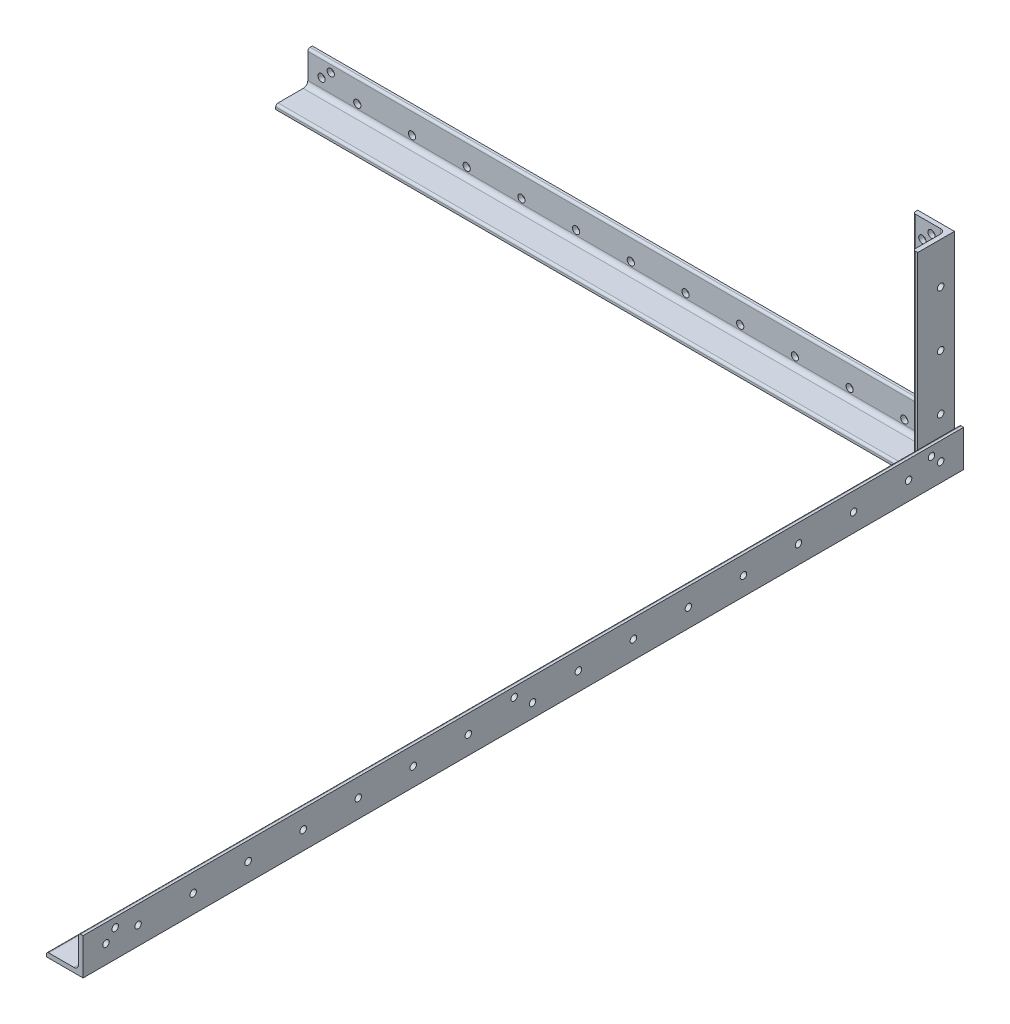
SolidWorks part; units mm, degrees
ref_plane "Front Plane" through (0, 0, 0) normal (0, 0, 1) x (1, 0, 0)
ref_plane "Top Plane" through (0, 0, 0) normal (0, 1, 0) x (1, 0, 0)
ref_plane "Right Plane" through (0, 0, 0) normal (1, 0, 0) x (0, 0, -1)
sketch "Sketch0" plane through (0, 0, 0) normal (0, 0, 1) x (1, 0, 0)
  line L0 (-12.7, -12.7) -> (12.7, -12.7)
  line L1 (12.7, -12.7) -> (12.7, 12.7)
  line L2 (12.7, 0) -> (0, 0) construction
  line L3 (0, 0) -> (0, -12.7) construction
  line L4 (9.525, -6.35) -> (9.525, 12.7) construction
  line L5 (6.35, -9.525) -> (-12.7, -9.525) construction
  arc A0 (9.525, -6.35) -> (6.35, -9.525) centre (6.35, -6.35) cw
  point P3 (8.5951, -8.5951)
  dimension "Inside Corner Radius" = 3.175
  dimension "Outside Height" = 25.4
  dimension "Inside Height" = 22.225
  dimension "Inside Width" = 22.225
  dimension "Wall Thickness" = 3.175
  dimension "D1" = 3.175
  dimension "Outside Width" = 25.4
sketch "Sketch1" plane through (0, 0, 0) normal (1, 0, 0) x (0, 0, -1)
  line L0 (304.8, 0) -> (-304.8, 0)
  point P4 (0, 0)
  dimension "Length" = 609.6
sketch "Sketch2" plane through (0, 0, 0) normal (0, 0, 1) x (1, 0, 0)
  line L0 (-12.7, -12.7) -> (12.7, -12.7)
  line L1 (12.7, -12.7) -> (12.7, 12.7)
  line L2 (12.7, 12.7) -> (9.525, 12.7) construction
  line L3 (9.525, 11.1125) -> (9.525, -6.35)
  line L4 (6.35, -9.525) -> (-11.1125, -9.525)
  line L5 (-12.7, -12.7) -> (-12.7, -9.525) construction
  line L6 (11.1125, 12.7) -> (12.7, 12.7)
  line L7 (-12.7, -11.1125) -> (-12.7, -12.7)
  line L8 (12.7, 0) -> (0, 0) construction
  line L9 (0, 0) -> (0, -12.7) construction
  arc A0 (9.525, 11.1125) -> (11.1125, 12.7) centre (11.1125, 11.1125) cw
  arc A1 (-12.7, -11.1125) -> (-11.1125, -9.525) centre (-11.1125, -11.1125) cw
  arc A2 (9.525, -6.35) -> (6.35, -9.525) centre (6.35, -6.35) cw
  dimension "Inside Radius" = 3.175
  dimension "Height" = 25.4
  dimension "Width" = 25.4
  dimension "Thickness" = 3.175
extrude "Boss-Extrude1" add sketch "Sketch2" along normal mid plane 609.6
sketch "Break Locations" plane through (0, 0, 0) normal (1, 0, 0) x (0, 0, -1)
  line L0 (-278.892, 0) -> (278.892, 0)
  line L1 (-304.8, -12.7) -> (-304.8, 12.7) construction
  line L2 (304.8, -12.7) -> (304.8, 12.7) construction
  point P0 (-283.21, 0)
  point P1 (283.21, 0)
  point P10 (0, 0)
  point P11 (278.892, 0)
  point P13 (-278.892, 0)
  dimension "D1" = 21.59
  dimension "D2" = 21.59
  dimension "D3" = 25.908
sketch "Sketch3" plane through (0, 0, -304.8) normal (0, 0, -1) x (-1, 0, 0)
  line L0 (-6.35, -9.525) -> (-6.35, 15.875)
  line L1 (-6.35, 15.875) -> (438.15, 15.875)
  line L2 (438.15, 15.875) -> (438.15, -9.525)
  line L3 (438.15, -9.525) -> (-6.35, -9.525)
  dimension "D1" = 25.4
  dimension "D2" = 444.5
extrude "Boss-Extrude2" add sketch "Sketch3" against normal blind 3.175 separate body
sketch "Sketch4" plane through (-438.15, 0, 0) normal (-1, 0, 0) x (0, 0, 1)
  line L1 (-304.8, -9.525) -> (-279.4, -9.525)
  line L2 (-304.8, -9.525) -> (-304.8, -6.35)
  line L3 (-304.8, -6.35) -> (-279.4, -6.35)
  line L4 (-279.4, -9.525) -> (-279.4, -6.35)
  dimension "D1" = 25.4
  dimension "D2" = 3.175
extrude "Boss-Extrude3" add sketch "Sketch4" against normal up to vertex (444.5 mm away) up to point (6.35, -9.525, -304.8)
fillet "Fillet1" radius 1.5875 2 edges at (-215.9, -6.35, -279.4) (-215.9, 15.875, -301.625)
fillet "Fillet2" radius 3.175 1 edges at (-215.9, -6.35, -301.625)
sketch "Sketch6" plane through (9.525, 0, 0) normal (-1, 0, 0) x (0, 0, 1)
  line L0 (-301.625, -3.175) -> (-301.625, 14.2875) construction
  line L1 (-301.625, -3.175) -> (-276.225, -3.175)
  line L2 (-301.625, -3.175) -> (-301.625, 0)
  line L3 (-301.625, 0) -> (-276.225, 0)
  line L4 (-276.225, -3.175) -> (-276.225, 0)
  line L5 (-301.625, -3.175) -> (-301.625, 14.2875) construction
  dimension "D1" = 25.4
  dimension "D2" = 3.175
extrude "Boss-Extrude4" add sketch "Sketch6" along normal blind 25.4 separate body
sketch "Sketch7" plane through (0, 0, 0) normal (0, 1, 0) x (1, 0, 0)
  line L1 (-15.875, 276.225) -> (6.35, 276.225)
  line L2 (-15.875, 276.225) -> (-15.875, 298.45)
  line L3 (-15.875, 298.45) -> (6.35, 298.45)
  line L4 (6.35, 276.225) -> (6.35, 298.45)
  dimension "D1" = 22.225
extrude "Cut-Extrude1" cut sketch "Sketch7" against normal blind 3.175
sketch "Sketch8" plane through (0, 0, 0) normal (0, 1, 0) x (1, 0, 0)
  line L6 (-15.875, 301.625) -> (-15.875, 298.45)
  line L7 (-15.875, 298.45) -> (6.35, 298.45)
  line L8 (6.35, 298.45) -> (6.35, 276.225)
  line L9 (6.35, 276.225) -> (9.525, 276.225)
  line L10 (9.525, 276.225) -> (9.525, 301.625)
  line L11 (9.525, 301.625) -> (-15.875, 301.625)
  line L12 (-15.875, 301.625) -> (-15.875, 298.45)
  line L13 (-15.875, 298.45) -> (6.35, 298.45)
  line L14 (6.35, 298.45) -> (6.35, 276.225)
  line L15 (6.35, 276.225) -> (9.525, 276.225)
  line L16 (9.525, 276.225) -> (9.525, 301.625)
  line L17 (9.525, 301.625) -> (-15.875, 301.625)
  dimension "D1" = 0
extrude "Boss-Extrude5" add sketch "Sketch8" along normal blind 130.175
fillet "Fillet3" radius 1.5875 2 edges at (6.35, 63.5, -276.225) (-15.875, 63.5, -298.45)
fillet "Fillet4" radius 3.175 1 edges at (6.35, 63.5, -298.45)
sketch "Sketch10" plane through (12.7, 0, 0) normal (1, 0, 0) x (0, 0, -1)
  line L1 (288.925, 0) -> (304.8, 0) construction
  line L2 (288.925, 0) -> (288.925, -12.7) construction
  line L3 (288.925, -12.7) -> (304.8, -12.7) construction
  line L4 (304.8, 0) -> (304.8, -12.7) construction
  line L5 (304.8, -12.7) -> (282.575, -12.7) construction
  line L6 (304.8, -12.7) -> (304.8, 6.35) construction
  line L7 (304.8, 6.35) -> (282.575, 6.35) construction
  line L8 (282.575, -12.7) -> (282.575, 6.35) construction
  circle A0 centre (282.575, 6.35) radius 2.25
  circle A1 centre (288.925, 0) radius 2.25
  dimension "D2" = 4.5
  dimension "D1" = 12.7
  dimension ".75" = 19.05
  dimension "D3" = 15.875
  dimension "D4" = 22.225
extrude "Cut-Extrude2" cut sketch "Sketch10" against normal blind 50.8
sketch "Sketch11" plane through (0, 0, -304.8) normal (0, 0, -1) x (-1, 0, 0)
  line L1 (-12.7, -12.7) -> (3.175, -12.7) construction
  line L2 (-12.7, -12.7) -> (-12.7, 3.175) construction
  line L3 (-12.7, 3.175) -> (3.175, 3.175) construction
  line L4 (3.175, -12.7) -> (3.175, 3.175) construction
  line L5 (-12.7, -12.7) -> (9.525, -12.7) construction
  line L6 (-12.7, -12.7) -> (-12.7, 9.525) construction
  line L7 (-12.7, 9.525) -> (9.525, 9.525) construction
  line L8 (9.525, -12.7) -> (9.525, 9.525) construction
  circle A0 centre (3.175, 3.175) radius 2.5
  circle A1 centre (9.525, 9.525) radius 2.5
  dimension "D3" = 5
  dimension "D1" = 15.875
  dimension "D2" = 22.225
  dimension "D4" = 15.875
  dimension "D5" = 22.225
extrude "Cut-Extrude3" cut sketch "Sketch11" against normal blind 50.8
sketch "Sketch12" plane through (12.7, 0, 0) normal (1, 0, 0) x (0, 0, -1)
  line L0 (0, 12.7) -> (0, -12.7) construction
  line L1 (-304.8, 12.7) -> (304.8, 12.7) construction
  line L2 (-304.8, -12.7) -> (304.8, -12.7) construction
  line L4 (-304.8, -12.7) -> (-304.8, 12.7) construction
  line L6 (-6.35, 6.35) -> (6.35, 6.35) construction
  line L7 (-6.35, 6.35) -> (-6.35, -3.175) construction
  line L8 (-6.35, -3.175) -> (6.35, -3.175) construction
  line L9 (6.35, 6.35) -> (6.35, -3.175) construction
  line L10 (-6.35, 6.35) -> (6.35, -3.175) construction
  line L11 (-6.35, -3.175) -> (6.35, 6.35) construction
  circle A0 centre (288.925, 0) radius 2.25 construction
  circle A1 centre (282.575, 6.35) radius 2.25 construction
  circle A2 centre (288.925, 0) radius 2.25
  circle A3 centre (282.575, 6.35) radius 2.25
  circle A4 centre (-288.925, 0) radius 2.25
  circle A5 centre (-282.575, 6.35) radius 2.25
  circle A19 centre (-6.35, 6.35) radius 2.25
  circle A20 centre (6.35, -3.175) radius 2.25
  circle A21 centre (-304.8, 0) radius 2.25 construction
  circle A22 centre (-266.7, 0) radius 2.25
  circle A23 centre (-228.6, 0) radius 2.25
  circle A24 centre (-190.5, 0) radius 2.25
  circle A25 centre (-152.4, 0) radius 2.25
  circle A26 centre (-114.3, 0) radius 2.25
  circle A27 centre (-76.2, 0) radius 2.25
  circle A28 centre (-38.1, 0) radius 2.25
  circle A76 centre (0, 0) radius 2.25 construction
  circle A77 centre (38.1, 0) radius 2.25
  circle A78 centre (76.2, 0) radius 2.25
  circle A79 centre (114.3, 0) radius 2.25
  circle A80 centre (152.4, 0) radius 2.25
  circle A81 centre (190.5, 0) radius 2.25
  circle A82 centre (228.6, 0) radius 2.25
  circle A83 centre (266.7, 0) radius 2.25
  circle A84 centre (304.8, 0) radius 2.25 construction
  point P44 (0, 1.5875)
  dimension "D2" = 22.225
  dimension "D3" = 9.525
  dimension "D4" = 6.35
  dimension "D5" = 12.7
  dimension "D1" = 17
extrude "Cut-Extrude4" cut sketch "Sketch12" against normal blind 50.8
sketch "Sketch13" plane through (0, 0, -304.8) normal (0, 0, -1) x (-1, 0, 0)
  line L0 (-12.7, -12.7) -> (-12.7, 12.7) construction
  line L1 (215.9, 15.875) -> (215.9, -9.525) construction
  line L2 (438.15, 15.875) -> (-6.35, 15.875) construction
  line L3 (-6.35, -9.525) -> (438.15, -9.525) construction
  circle A0 centre (-12.7, 0) radius 2.5 construction
  circle A1 centre (25.172, 0) radius 2.5
  circle A2 centre (63.0441, 0) radius 2.5
  circle A3 centre (100.9161, 0) radius 2.5
  circle A4 centre (138.7882, 0) radius 2.5
  circle A5 centre (176.6602, 0) radius 2.5
  circle A6 centre (214.5323, 0) radius 2.5
  circle A7 centre (252.4043, 0) radius 2.5
  circle A8 centre (290.2764, 0) radius 2.5
  circle A9 centre (328.1484, 0) radius 2.5
  circle A10 centre (366.0205, 0) radius 2.5
  circle A11 centre (403.8925, 0) radius 2.5
  circle A12 centre (441.7645, 0) radius 2.5 construction
  circle A13 centre (3.175, 3.175) radius 2.5 construction
  circle A14 centre (3.175, 3.175) radius 2.5
  circle A15 centre (9.525, 9.525) radius 2.5 construction
  circle A16 centre (9.525, 9.525) radius 2.5
  circle A17 centre (428.625, 3.175) radius 2.5
  circle A18 centre (422.275, 9.525) radius 2.5
  dimension "D2" = 22.225
  dimension "D1" = 13
extrude "Cut-Extrude5" cut sketch "Sketch13" against normal blind 50.8
sketch "Sketch14" plane through (0, 0, -304.8) normal (0, 0, -1) x (-1, 0, 0)
  line L0 (12.7, -12.7) -> (-12.7, -12.7) construction
  line L1 (-9.525, 63.5) -> (15.875, 63.5) construction
  line L2 (-9.525, 130.175) -> (-9.525, -3.175) construction
  line L3 (15.875, 130.175) -> (15.875, -3.175) construction
  circle A0 centre (0, -12.7) radius 2.5 construction
  circle A1 centre (0, 25.4) radius 2.5
  circle A2 centre (0, 63.5) radius 2.5
  circle A3 centre (0, 101.6) radius 2.5
  circle A4 centre (0, 139.7) radius 2.5
  circle A5 centre (3.175, 3.175) radius 2.5 construction
  circle A6 centre (9.525, 9.525) radius 2.5 construction
  circle A7 centre (3.175, 3.175) radius 2.5
  circle A8 centre (9.525, 9.525) radius 2.5
  circle A9 centre (3.175, 123.825) radius 2.5
  circle A10 centre (9.525, 117.475) radius 2.5
  dimension "D2" = 38.1
  dimension "D1" = 5
extrude "Cut-Extrude6" cut sketch "Sketch14" against normal blind 50.8
sketch "Sketch15" plane through (0, -12.7, 0) normal (0, -1, 0) x (1, 0, 0)
  circle A0 centre (4.102, -296.8961) radius 2.4715
  circle A1 centre (-8.1243, -284.9273) radius 2.8266
sketch "Sketch16" plane through (0, 0, -304.8) normal (0, 0, -1) x (-1, 0, 0)
  line L0 (-6.35, -9.525) -> (438.15, -9.525) construction
  line L1 (-6.35, 15.875) -> (-6.35, -9.525) construction
  circle A0 centre (3.175, 3.175) radius 2.5 construction
  circle A1 centre (9.525, 9.525) radius 2.5 construction
  circle A2 centre (25.172, 0) radius 2.5 construction
  circle A3 centre (3.175, 3.175) radius 2.5
  circle A4 centre (9.525, 9.525) radius 2.5
  circle A5 centre (25.172, 0) radius 2.5
  dimension "D1" = 12.7
  dimension "D2" = 9.525
  dimension "D3" = 19.05
  dimension "D4" = 9.525
sketch "Sketch17" plane through (0, 0, -301.625) normal (0, 0, -1) x (-1, 0, 0)
  line L0 (15.875, -3.175) -> (-9.525, -3.175) construction
  line L1 (-9.525, 130.175) -> (-9.525, -3.175) construction
  circle A0 centre (0, 25.4) radius 2.5 construction
  circle A1 centre (9.525, 9.525) radius 2.5 construction
  circle A2 centre (3.175, 3.175) radius 2.5 construction
  circle A3 centre (0, 25.4) radius 2.5
  circle A4 centre (9.525, 9.525) radius 2.5
  circle A5 centre (3.175, 3.175) radius 2.5
  dimension "D1" = 6.35
  dimension "D2" = 12.7
  dimension "D3" = 12.7
  dimension "D4" = 19.05
sketch "Sketch18" plane through (9.525, 0, 0) normal (1, 0, 0) x (0, 0, -1)
  line L0 (-304.8, -12.7) -> (304.8, -12.7) construction
  line L1 (304.8, 15.875) -> (304.8, -9.525) construction
  circle A0 centre (292.1, 25.4) radius 2.25
  circle A2 centre (282.575, 6.35) radius 2.25 construction
  circle A3 centre (292.1, 63.5) radius 2.25
  circle A4 centre (292.1, 101.6) radius 2.25
  dimension "D1" = 38.1
  dimension "D2" = 12.7
  dimension "D3" = 3
extrude "Cut-Extrude7" cut sketch "Sketch18" against normal blind 25.4
sketch "Sketch19" plane through (9.525, 0, 0) normal (1, 0, 0) x (0, 0, -1)
  line L0 (301.625, -3.175) -> (276.225, -3.175) construction
  line L1 (301.625, 130.175) -> (301.625, -3.175) construction
  circle A0 centre (288.925, 0) radius 2.25 construction
  circle A1 centre (282.575, 6.35) radius 2.25 construction
  circle A2 centre (288.925, 0) radius 2.25
  circle A3 centre (282.575, 6.35) radius 2.25
  dimension "D1" = 9.525
  dimension "D2" = 3.175
  dimension "D3" = 19.05
  dimension "D4" = 12.7
equation "\"D1@Break Locations\" = .85 * \"Height@Sketch2\""
equation "\"D2@Break Locations\"=\"D1@Break Locations\""
equation "\"Thickness@Sketch2\" = \"Wall Thickness@Sketch0\""
equation "\"Height@Sketch2\" = \"Outside Height@Sketch0\""
equation "\"Width@Sketch2\" = \"Outside Width@Sketch0\""
equation "\"Inside Radius@Sketch2\" = \"Inside Corner Radius@Sketch0\""
equation "\"Length@Boss-Extrude1\" = \"Length@Sketch1\""
equation "\"D3@Break Locations\"=\"D2@Break Locations\"*1.2"
equation "\"D1@Sketch0\"=\"Wall Thickness@Sketch0\""
